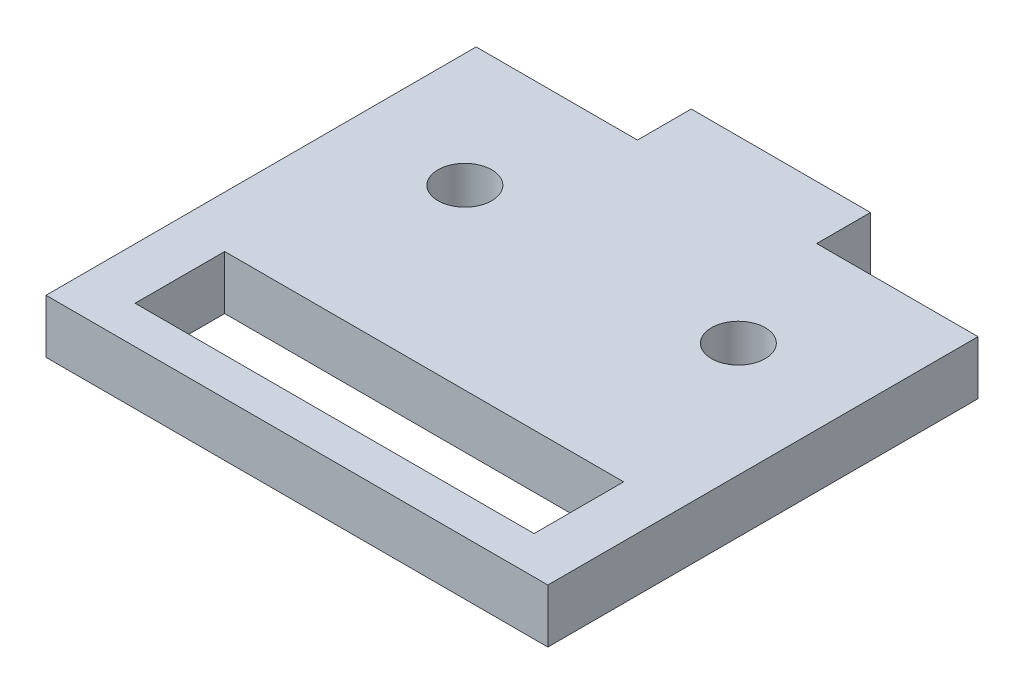
SolidWorks part; units mm, degrees
ref_plane "Front Plane" through (0, 0, 0) normal (0, 0, 1) x (1, 0, 0)
ref_plane "Top Plane" through (0, 0, 0) normal (0, 1, 0) x (1, 0, 0)
ref_plane "Right Plane" through (0, 0, 0) normal (1, 0, 0) x (0, 0, -1)
sketch "Sketch1" plane through (0, 0, 0) normal (0, 1, 0) x (1, 0, 0)
  line L0 (-5, 3) -> (5, 3)
  line L2 (5, 3) -> (14, 3)
  line L3 (14, 3) -> (14, 27)
  line L4 (14, 27) -> (5, 27)
  line L5 (11.13, 5.1) -> (11.13, 10.1)
  line L6 (11.13, 10.1) -> (-11.13, 10.1)
  line L7 (5, 27) -> (5, 30)
  line L8 (-11.13, 5.1) -> (11.13, 5.1)
  line L9 (0, 25) -> (0, 10.1) construction
  line L10 (-11.13, 5.1) -> (-11.13, 10.1)
  line L11 (-14, 3) -> (-14, 27)
  line L12 (-5, 3) -> (-14, 3)
  line L15 (5, 30) -> (-5, 30)
  line L16 (-5, 30) -> (-5, 27)
  line L17 (-5, 27) -> (-14, 27)
  circle A0 centre (7.63, 20) radius 1.5
  circle A1 centre (-7.63, 20) radius 1.5
  dimension "D9" = 3
  dimension "D2" = 10
  dimension "D3" = 9
  dimension "D4" = 6.37
  dimension "D5" = 7
  dimension "D6" = 24
  dimension "D7" = 2.1
  dimension "D8" = 5
  dimension "D10" = 22.26
  dimension "D11" = 3
  dimension "D12" = 10
  dimension "D13" = 3
  dimension "D14" = 14
extrude "Boss-Extrude1" add sketch "Sketch1" along normal blind 3
